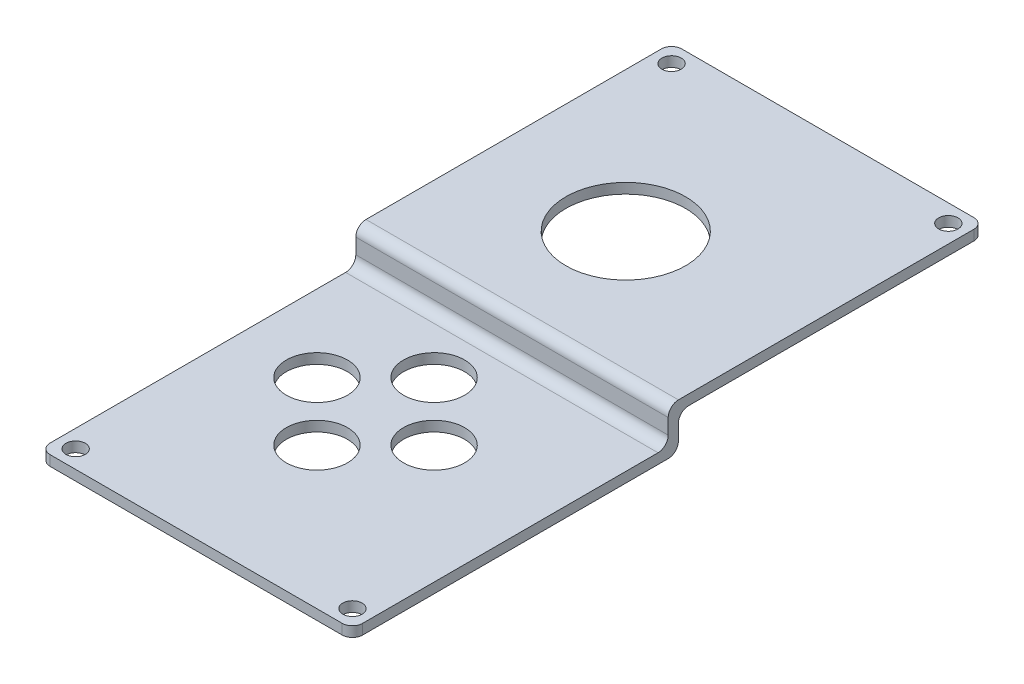
SolidWorks part; units mm, degrees
ref_plane "Front Plane" through (0, 0, 0) normal (0, 0, 1) x (1, 0, 0)
ref_plane "Top Plane" through (0, 0, 0) normal (0, 1, 0) x (1, 0, 0)
ref_plane "Right Plane" through (0, 0, 0) normal (1, 0, 0) x (0, 0, -1)
sketch "Sketch2" plane through (0, 0, 0) normal (1, 0, 0) x (0, 0, -1)
  line L0 (0, 0) -> (60, 0)
  line L1 (0, 0) -> (0, -7)
  line L2 (0, -7) -> (-64, -7)
  line L3 (60, 0) -> (60, 2)
  line L4 (60, 2) -> (-2, 2)
  line L5 (-2, 2) -> (-2, -5)
  line L6 (-2, -5) -> (-64, -5)
  line L7 (-64, -5) -> (-64, -7)
  dimension "D1" = 60
  dimension "D2" = 7
  dimension "D3" = 64
  dimension "D4" = 2
  dimension "D5" = 2
  dimension "D6" = 2
extrude "Boss-Extrude1" add sketch "Sketch2" along normal blind 61.34
sketch "Sketch3" plane through (0, 2, 0) normal (0, 1, 0) x (1, 0, 0)
  line L0 (27.5, 60) -> (27.5, 23.5) construction
  line L1 (61.34, 60) -> (0, 60) construction
  line L2 (0, 60) -> (0, -2) construction
  line L3 (0, 56.5) -> (3.5, 56.5) construction
  line L4 (61.34, 56.5) -> (57.84, 56.5) construction
  line L6 (61.34, 60) -> (61.34, -2) construction
  circle A0 centre (27.5, 23.5) radius 11.75
  circle A1 centre (57.84, 56.5) radius 1.9
  circle A2 centre (3.5, 56.5) radius 1.9
  dimension "D3" = 23.5
  dimension "D8" = 3.8
  dimension "D9" = 3.8
  dimension "D1" = 36.5
  dimension "D2" = 27.5
  dimension "D4" = 3.5
  dimension "D5" = 3.5
  dimension "D6" = 3.5
  dimension "D7" = 3.5
sketch "Sketch4" plane through (0, -5, 0) normal (0, 1, 0) x (1, 0, 0)
  line L0 (15.07, -64) -> (15.07, -24.7) construction
  line L1 (61.34, -64) -> (0, -64) construction
  line L2 (15.07, -24.7) -> (0, -24.7) construction
  line L3 (0, -2) -> (0, -64) construction
  line L4 (15.07, -24.7) -> (38.07, -24.7) construction
  line L5 (26.57, -13.2) -> (26.57, -36.2) construction
  line L6 (61.34, -60.5) -> (57.84, -60.5) construction
  line L7 (61.34, -2) -> (61.34, -64) construction
  line L8 (0, -60.5) -> (3.5, -60.5) construction
  circle A0 centre (38.07, -24.7) radius 6
  circle A1 centre (26.57, -36.2) radius 6
  circle A2 centre (15.07, -24.7) radius 6
  circle A3 centre (26.57, -13.2) radius 6
  circle A4 centre (57.84, -60.5) radius 1.9
  circle A5 centre (3.5, -60.5) radius 1.9
  point P10 (26.57, -24.7)
  point P11 (26.57, -24.7)
  dimension "D5" = 12
  dimension "D6" = 12
  dimension "D7" = 12
  dimension "D8" = 12
  dimension "D13" = 3.8
  dimension "D14" = 3.8
  dimension "D1" = 39.3
  dimension "D2" = 15.07
  dimension "D3" = 23
  dimension "D4" = 23
  dimension "D9" = 3.5
  dimension "D10" = 3.5
  dimension "D11" = 3.5
  dimension "D12" = 3.5
extrude "Cut-Extrude1" cut sketch "Sketch3" against normal through all
extrude "Cut-Extrude2" cut sketch "Sketch4" against normal through all
fillet "Fillet1" radius 2 4 edges at (30.67, 0, 0) (30.67, -7, 0) (30.67, 2, 2) (30.67, -5, 2)
fillet "Fillet3" radius 2 4 edges at (61.34, 1, -60) (61.34, -6, 64) (0, -6, 64) (0, 1, -60)
